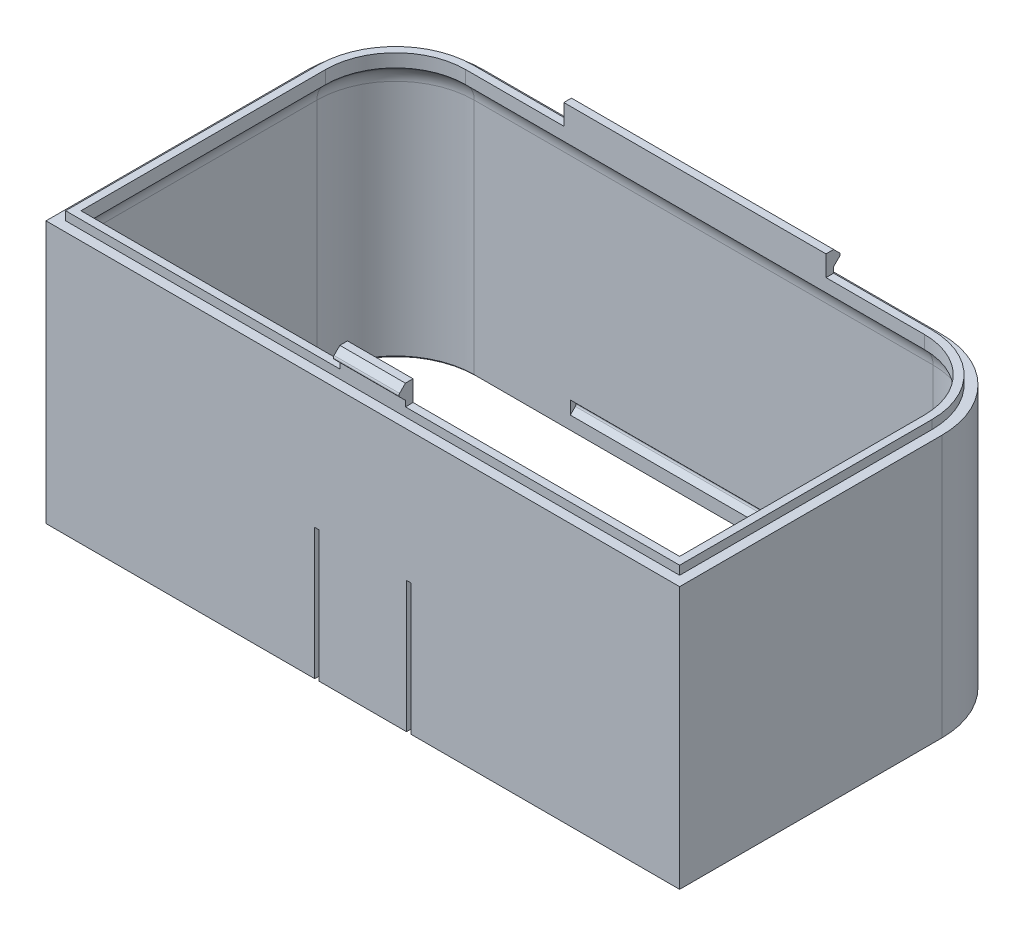
SolidWorks part; units mm, degrees
material "ПК/АБС"
ref_plane "Спереди" through (0, 0, 0) normal (0, 0, 1) x (1, 0, 0)
ref_plane "Сверху" through (0, 0, 0) normal (0, 1, 0) x (1, 0, 0)
ref_plane "Справа" through (0, 0, 0) normal (1, 0, 0) x (0, 0, -1)
sketch "Эскиз1" plane through (0, 0, 0) normal (0, 1, 0) x (1, 0, 0)
  line L0 (-70.5, 2) -> (70.5, 2)
  line L1 (-72.5, 0) -> (72.5, 0)
  line L2 (-72.5, 0) -> (-72.5, 60)
  line L3 (-52.5, 80) -> (52.5, 80)
  line L4 (72.5, 0) -> (72.5, 60)
  line L9 (70.5, 2) -> (70.5, 60)
  line L10 (-52.5, 78) -> (52.5, 78)
  line L11 (-70.5, 2) -> (-70.5, 60)
  arc A0 (72.5, 60) -> (52.5, 80) centre (52.5, 60) ccw
  arc A1 (-52.5, 80) -> (-72.5, 60) centre (-52.5, 60) ccw
  arc A2 (70.5, 60) -> (52.5, 78) centre (52.5, 60) ccw
  arc A3 (-52.5, 78) -> (-70.5, 60) centre (-52.5, 60) ccw
  point P8 (72.5, 80)
  point P11 (-72.5, 80)
  dimension "D3" = 20
  dimension "D1" = 80
  dimension "D2" = 145
  dimension "D4" = 2
extrude "Бобышка-Вытянуть1" add sketch "Эскиз1" along normal blind 60
sketch "Эскиз2" plane through (0, 60, 0) normal (0, 1, 0) x (1, 0, 0)
  line L0 (-68.5, 60) -> (-68.5, 4)
  line L1 (-68.5, 4) -> (68.5, 4)
  line L2 (68.5, 4) -> (68.5, 60)
  line L3 (52.5, 76) -> (-52.5, 76)
  line L4 (-72.5, 60) -> (-72.5, 0)
  line L5 (-72.5, 0) -> (72.5, 0)
  line L6 (72.5, 0) -> (72.5, 60)
  line L7 (52.5, 80) -> (-52.5, 80)
  line L8 (-72.5, 60) -> (-72.5, 0)
  line L9 (-72.5, 0) -> (72.5, 0)
  line L10 (72.5, 0) -> (72.5, 60)
  line L11 (52.5, 80) -> (-52.5, 80)
  arc A0 (68.5, 60) -> (52.5, 76) centre (52.5, 60) ccw
  arc A1 (-52.5, 76) -> (-68.5, 60) centre (-52.5, 60) ccw
  arc A2 (72.5, 60) -> (52.5, 80) centre (52.5, 60) ccw
  arc A3 (-52.5, 80) -> (-72.5, 60) centre (-52.5, 60) ccw
  arc A4 (72.5, 60) -> (52.5, 80) centre (52.5, 60) ccw
  arc A5 (-52.5, 80) -> (-72.5, 60) centre (-52.5, 60) ccw
  dimension "D1" = 0
  dimension "D2" = 4
extrude "Бобышка-Вытянуть2" add sketch "Эскиз2" against normal blind 1
chamfer "Фаска3" distance 2 angle 45 6 edges at (70.5, 59, -31) (65.2279, 59, -72.7279) (0, 59, -78) (-65.2279, 59, -72.7279) (0, 59, -2) (-70.5, 59, -31)
sketch "Эскиз11" plane through (0, 60, 0) normal (0, 1, 0) x (1, 0, 0)
  line L0 (68.5, 4) -> (68.5, 60) construction
  line L1 (-68.5, 4) -> (68.5, 4) construction
  line L2 (-68.5, 60) -> (-68.5, 4) construction
  line L3 (52.5, 76) -> (-52.5, 76) construction
  line L4 (68.5, 4) -> (68.5, 60)
  line L5 (-68.5, 4) -> (68.5, 4)
  line L6 (-68.5, 60) -> (-68.5, 4)
  line L7 (52.5, 76) -> (-52.5, 76)
  line L8 (70.25, 2.25) -> (70.25, 60)
  line L9 (52.5, 77.75) -> (-52.5, 77.75)
  line L10 (-70.25, 60) -> (-70.25, 2.25)
  line L11 (-70.25, 2.25) -> (70.25, 2.25)
  arc A0 (68.5, 60) -> (52.5, 76) centre (52.5, 60) ccw construction
  arc A1 (-52.5, 76) -> (-68.5, 60) centre (-52.5, 60) ccw construction
  arc A2 (68.5, 60) -> (52.5, 76) centre (52.5, 60) ccw
  arc A3 (-52.5, 76) -> (-68.5, 60) centre (-52.5, 60) ccw
  arc A4 (70.25, 60) -> (52.5, 77.75) centre (52.5, 60) ccw
  arc A5 (-52.5, 77.75) -> (-70.25, 60) centre (-52.5, 60) ccw
  dimension "D1" = 1.75
extrude "Бобышка-Вытянуть8" add sketch "Эскиз11" along normal blind 2
sketch "Эскиз12" plane through (0, 0, 0) normal (1, 0, 0) x (0, 0, -1)
  line L0 (76, 59) -> (76, 62) construction
  line L1 (76, 59) -> (76, 62) construction
  line L2 (76, 62) -> (76, 66.7)
  line L3 (76, 66.7) -> (77.75, 66.7)
  line L4 (77.75, 66.7) -> (79.45, 65)
  line L5 (79.45, 65) -> (77.75, 63.3)
  line L6 (77.75, 63.3) -> (77.75, 62)
  line L7 (77.75, 62) -> (76, 62)
  line L9 (80, 60) -> (60, 60) construction
  dimension "D1" = 1.7
  dimension "D2" = 5
extrude "Бобышка-Вытянуть9" add sketch "Эскиз12" along normal mid plane 60
sketch "Эскиз13" plane through (0, 0, 0) normal (1, 0, 0) x (0, 0, -1)
  line L0 (2.25, 62) -> (2.25, 63.3)
  line L1 (2.25, 63.3) -> (0.55, 65)
  line L2 (0.55, 65) -> (2.25, 66.7)
  line L3 (2.25, 66.7) -> (4, 66.7)
  line L4 (4, 66.7) -> (4, 62)
  line L5 (2.25, 62) -> (60, 62) construction
  line L6 (4, 62) -> (2.25, 62)
  line L7 (4, 59) -> (4, 62) construction
  line L8 (4, 59) -> (4, 62) construction
  line L9 (0, 60) -> (60, 60) construction
  dimension "D1" = 5
  dimension "D2" = 1.7
extrude "Бобышка-Вытянуть10" add sketch "Эскиз13" along normal mid plane 15
sketch "Эскиз15" plane through (0, 0, 0) normal (1, 0, 0) x (0, 0, -1)
  line L0 (2, 3.5) -> (2, 6.5)
  line L1 (2, 6.5) -> (0.5, 5)
  line L2 (0.5, 5) -> (2, 3.5)
  line L3 (0, 60) -> (0, 0) construction
  line L4 (0, 0) -> (60, 0) construction
  dimension "D1" = 2
  dimension "D2" = 1.5
  dimension "D3" = 5
extrude "Вырез-Вытянуть2" cut sketch "Эскиз15" against normal mid plane 16
sketch "Эскиз16" plane through (0, 0, 0) normal (1, 0, 0) x (0, 0, -1)
  line L0 (78, 3.5) -> (78, 6.5)
  line L1 (78, 6.5) -> (79.5, 5)
  line L2 (79.5, 5) -> (78, 3.5)
  line L3 (60, 0) -> (80, 0) construction
  dimension "D1" = 2
  dimension "D2" = 1.5
  dimension "D3" = 5
extrude "Вырез-Вытянуть3" cut sketch "Эскиз16" against normal mid plane 61
chamfer "Фаска6" distance 0.5 angle 45 6 edges at (-70.5, 0, -31) (-65.2279, 0, -72.7279) (0, 0, -78) (65.2279, 0, -72.7279) (0, 0, -2) (70.5, 0, -31)
fillet "Скругление3" radius 5 6 edges at (70.5, 57, -31) (65.2279, 57, -72.7279) (0, 57, -78) (-65.2279, 57, -72.7279) (0, 57, -2) (-70.5, 57, -31)
fillet "Скругление4" radius 0.5 2 edges at (0, 5, -0.5) (0, 5, -79.5)
fillet "Скругление5" radius 0.5 2 edges at (0, 65, -79.45) (0, 65, -0.55)
sketch "Эскиз18" plane through (0, 0, 0) normal (0, 0, 1) x (1, 0, 0)
  line L0 (-72.5, 0) -> (72.5, 0) construction
  line L1 (-11, 30) -> (-10, 30)
  line L2 (-11, 30) -> (-11, 0)
  line L3 (-11, 0) -> (-10, 0)
  line L4 (-10, 30) -> (-10, 0)
  line L5 (-10, 30) -> (10, 30) construction
  line L6 (10, 30) -> (11, 30)
  line L7 (10, 30) -> (10, 0)
  line L8 (10, 0) -> (11, 0)
  line L9 (11, 30) -> (11, 0)
  line L10 (0, 0) -> (0, 30) construction
  dimension "D1" = 20
  dimension "D2" = 1
  dimension "D3" = 30
extrude "Вырез-Вытянуть4" cut sketch "Эскиз18" against normal up to surface (2 mm away) up to face at (0, 5, -2)
